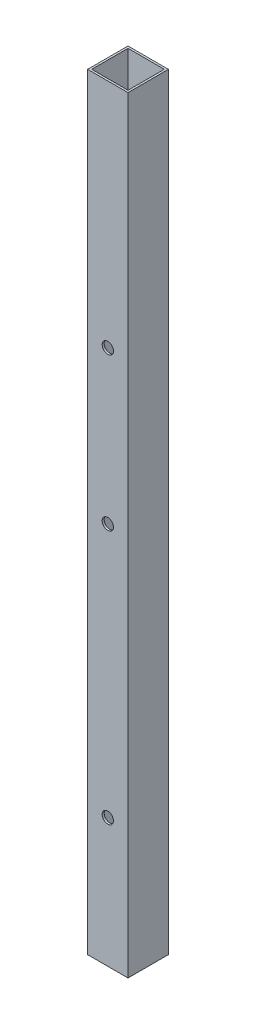
SolidWorks part; units mm, degrees
ref_plane "Front Plane" through (0, 0, 0) normal (0, 0, 1) x (1, 0, 0)
ref_plane "Top Plane" through (0, 0, 0) normal (0, 1, 0) x (1, 0, 0)
ref_plane "Right Plane" through (0, 0, 0) normal (1, 0, 0) x (0, 0, -1)
sketch "Sketch1" plane through (0, 0, 0) normal (0, 1, 0) x (1, 0, 0)
  line L0 (0, 0) -> (0, 25.4)
  line L1 (0, 25.4) -> (25.4, 25.4)
  line L2 (25.4, 25.4) -> (25.4, 0)
  line L3 (25.4, 0) -> (0, 0)
  line L6 (1.27, 12.3615) -> (1.27, 24.13)
  line L7 (1.27, 24.13) -> (12.7, 24.13)
  line L10 (12.7, 24.13) -> (24.13, 24.13)
  line L11 (24.13, 24.13) -> (24.13, 12.7)
  line L12 (24.13, 1.27) -> (24.13, 12.7)
  line L13 (24.13, 1.27) -> (12.7, 1.27)
  line L14 (1.27, 1.27) -> (12.7, 1.27)
  line L15 (1.27, 12.3615) -> (1.27, 1.27)
  dimension "D1" = 25.4
  dimension "D2" = 25.4
  dimension "D3" = 11.7685
  dimension "D4" = 11.0915
  dimension "D5" = 11.43
  dimension "D6" = 11.43
extrude "Boss-Extrude1" add sketch "Sketch1" along normal blind 482.6
sketch "Sketch3" plane through (0, 0, -25.4) normal (0, 0, -1) x (-1, 0, 0)
  circle A0 centre (-12.762, 449.168) radius 2.54
extrude "Cut-Extrude1" cut sketch "Sketch3" against normal blind 2.54
sketch "Sketch4" plane through (0, 0, -25.4) normal (0, 0, -1) x (-1, 0, 0)
  circle A1 centre (-12.7006, 321.2008) radius 2.54
extrude "Cut-Extrude2" cut sketch "Sketch4" against normal blind 2.54
sketch "Sketch5" plane through (0, 0, -25.4) normal (0, 0, -1) x (-1, 0, 0)
  circle A0 centre (-12.716, 18.4179) radius 2.54
extrude "Cut-Extrude3" cut sketch "Sketch5" against normal blind 2.54
sketch "Sketch6" plane through (0, 0, 0) normal (0, 0, 1) x (1, 0, 0)
  circle A0 centre (12.7, 81.078) radius 3.556
extrude "Cut-Extrude4" cut sketch "Sketch6" against normal blind 2.54
sketch "Sketch7" plane through (0, 0, 0) normal (0, 0, 1) x (1, 0, 0)
  circle A0 centre (12.7, 241.126) radius 3.556
  circle A1 centre (12.7, 337.126) radius 3.556
extrude "Cut-Extrude5" cut sketch "Sketch7" against normal blind 2.54
